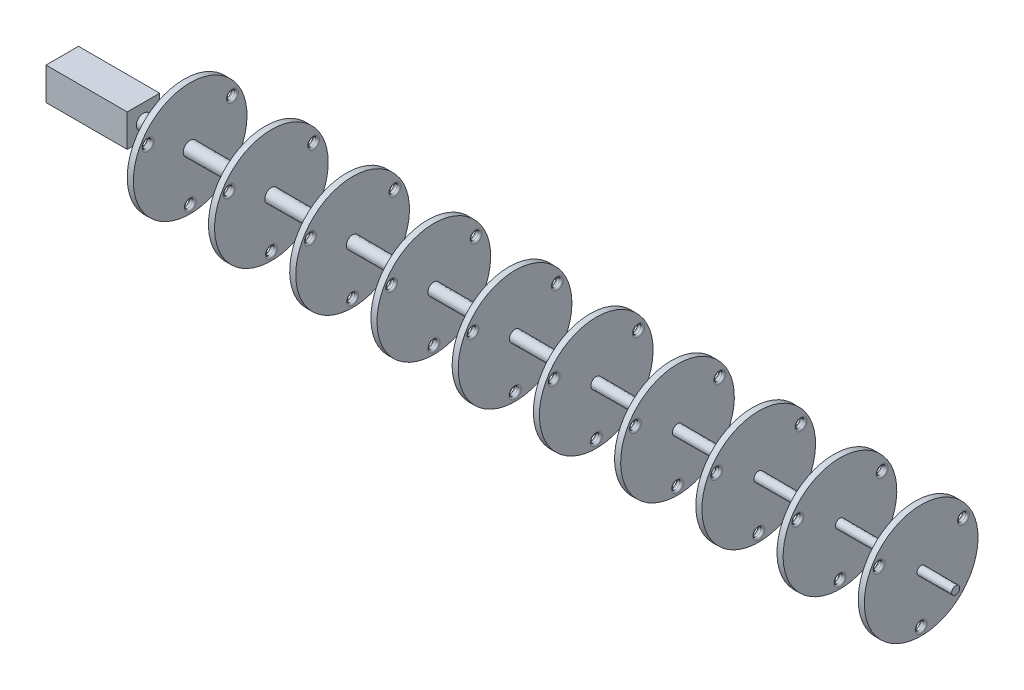
SolidWorks part; units mm, degrees
ref_plane "Front Plane" through (0, 0, 0) normal (0, 0, 1) x (1, 0, 0)
ref_plane "Top Plane" through (0, 0, 0) normal (0, 1, 0) x (1, 0, 0)
ref_plane "Right Plane" through (0, 0, 0) normal (1, 0, 0) x (0, 0, -1)
sketch "Sketch2" plane through (0, 0, 0) normal (0, 0, 1) x (1, 0, 0)
  line L0 (0, 1.75) -> (200, 1)
  line L1 (0, -11) -> (0, 11) construction
  line L2 (200, 1) -> (200, 0)
  line L3 (200, 0) -> (0, 0)
  line L4 (0, 0) -> (0, 1.75)
  dimension "D1" = 1.75
  dimension "D2" = 200
  dimension "D3" = 1
revolve "Revolve1" add sketch "Sketch2" angle 360 about L3
ref_axis "Axis1" through (-3.9062, 0, 0) along (1, 0, 0)
sketch "Sketch3" plane through (0, 0, 0) normal (0, 0, 1) x (1, 0, 0)
  line L0 (10, 0) -> (10, 14)
  line L1 (10, 14) -> (11.5, 14)
  line L2 (11.5, 14) -> (11.5, 0)
  line L3 (11.5, 0) -> (10, 0)
  line L4 (0, -14.3) -> (0, 14.3) construction
  dimension "D1" = 1.5
  dimension "D2" = 14
  dimension "D3" = 10
revolve "Revolve2" add sketch "Sketch3" angle 360 about L3
sketch "Sketch5" plane through (11.5, 0, 0) normal (1, 0, 0) x (0, 0, -1)
  line L0 (0, -12) -> (0, 0) construction
  line L1 (0, 0) -> (10.3923, 6) construction
  line L2 (-10.3923, 6) -> (0, 0) construction
  line L3 (0, 14.3) -> (0, -14.3) construction
  circle A0 centre (0, -12) radius 1
  circle A1 centre (10.3923, 6) radius 1
  circle A2 centre (-10.3923, 6) radius 1
  dimension "D2" = 2
  dimension "D1" = 12
  dimension "D3" = 120
  dimension "D4" = 120
extrude "Cut-Extrude1" cut sketch "Sketch5" against normal up to next
fillet "Fillet1" radius 0.5 6 edges at (10, 5, -10.3923) (10, -13, 0) (11.5, -11, 0) (11.5, 7, -10.3923) (10, 5, 10.3923) (11.5, 7, 10.3923)
pattern_linear "LPattern1" count 10 spacing 20 along (1, 0, 0) of "Revolve2", "Cut-Extrude1", "Fillet1"
sketch "Sketch16" plane through (0, 0, 0) normal (-1, 0, 0) x (0, 0, 1)
  line L1 (-4, -4) -> (4, -4)
  line L2 (-4, -4) -> (-4, 4)
  line L3 (-4, 4) -> (4, 4)
  line L4 (4, -4) -> (4, 4)
  line L5 (-4, -4) -> (4, 4) construction
  line L6 (-4, 4) -> (4, -4) construction
  point P0 (0, 0)
  dimension "D1" = 8
extrude "Boss-Extrude1" add sketch "Sketch16" along normal blind 20
equation "\"R_initial\"= 1.75"
equation "\"D1@Sketch2\"=\"R_initial\""
equation "\"R_distal\"= 1"
equation "\"D3@Sketch2\"=\"R_distal\""
equation "\"L\"=200"
equation "\"D2@Sketch2\"=\"L\""
equation "\"disk_thickness\"= 1.5"
equation "\"D1@Sketch3\"=\"disk_thickness\""
equation "\"disk_radius\" = 14"
equation "\"D2@Sketch3\"=\"disk_radius\""
equation "\"disk_spacing_initial\"= 10"
equation "\"D3@Sketch3\"=\"disk_spacing_initial\""
equation "\"tendon_routing_radius\"= 12"
equation "\"D1@Sketch5\"=\"tendon_routing_radius\""
equation "\"tendon_routing_hole_radius\"=2"
equation "\"D2@Sketch5\"=\"tendon_routing_hole_radius\""
equation "\"tendon_routing_hole_fillet\"=0.5"
equation "\"D1@Fillet1\"=\"tendon_routing_hole_fillet\""
equation "\"inter_disk_spacing\"= 20"
equation "\"D3@LPattern1\"=\"inter_disk_spacing\""
equation "\"num_disk\"= 10"
equation "\"D1@LPattern1\"=\"num_disk\""
